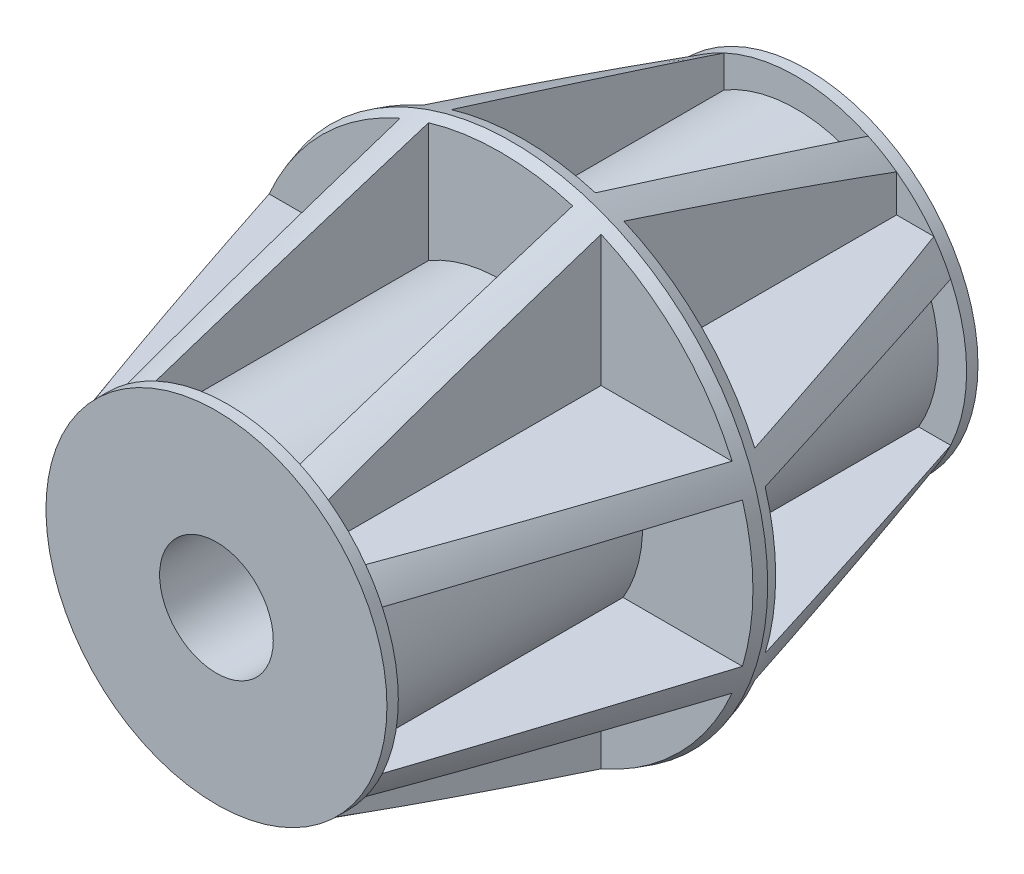
SolidWorks part; units mm, degrees
note: The reader was unsure of these and kept them because the rebuilt part matched: shared geometry of "Cross Cut Sketch<2>".
ref_plane "Front Plane" through (0, 0, 0) normal (0, 0, 1) x (1, 0, 0)
ref_plane "Top Plane" through (0, 0, 0) normal (0, 1, 0) x (1, 0, 0)
ref_plane "Right Plane" through (0, 0, 0) normal (1, 0, 0) x (0, 0, -1)
sketch "Front Connector Sketch" plane through (0, 0, 0) normal (0, 0, 1) x (1, 0, 0)
  circle A0 centre (0, 0) radius 30
  dimension "D1" = 60
extrude "Front Connector Extrude" add sketch "Front Connector Sketch" against normal blind 2
ref_plane "Back Plane" through (0, 0, 100) normal (0, 0, 1) x (1, 0, 0)
sketch "Back Connector Sketch" plane through (0, 0, 100) normal (0, 0, 1) x (1, 0, 0)
  circle A0 centre (0, 0) radius 30
  circle A1 centre (0, 0) radius 30 construction
extrude "Back Connector Extrude" add sketch "Back Connector Sketch" along normal blind 2 separate body
ref_plane "Mid Plane" through (0, 0, 50) normal (0, 0, 1) x (1, 0, 0)
sketch "Mid Ring Sketch" plane through (0, 0, 50) normal (0, 0, 1) x (1, 0, 0)
  circle A0 centre (0, 0) radius 45
  dimension "D1" = 90
loft "Front Loft" add profiles "Mid Ring Sketch" section face at (30, 0, 0) section "Mid Ring Sketch" connector at (0.9235, -29.9858, 0) connector at (0.2748, -44.9992, 50)
loft "Back Loft" add section edge at (45, 0, 50) section face at (30, 0, 100) connector at (44.9951, 0.6652, 50) connector at (29.9954, 0.5232, 100)
sketch "Cross Cut Sketch" plane through (0, 0, 50) normal (0, 0, 1) x (1, 0, 0)
  line L0 (-12.6777, 43.1773) -> (-12.6777, 21.5471)
  line L1 (-12.6777, 21.5471) -> (-12.6777, 17.6777) construction
  line L2 (-12.6777, -21.5471) -> (-12.6777, -43.1773)
  line L3 (12.6777, 43.1773) -> (12.6777, 21.5471)
  line L4 (12.6777, 21.5471) -> (12.6777, 17.6777) construction
  line L5 (12.6777, -21.5471) -> (12.6777, -43.1773)
  line L6 (17.6777, 41.3824) -> (17.6777, 17.6777)
  line L7 (17.6777, 12.6777) -> (17.6777, -12.6777) construction
  line L8 (17.6777, -17.6777) -> (17.6777, -41.3824)
  line L9 (-17.6777, 41.3824) -> (-17.6777, 17.6777)
  line L10 (-17.6777, 12.6777) -> (-17.6777, -12.6777) construction
  line L11 (-17.6777, -17.6777) -> (-17.6777, -41.3824)
  line L16 (-41.3824, 17.6777) -> (-17.6777, 17.6777)
  line L17 (-12.6777, 17.6777) -> (12.6777, 17.6777) construction
  line L18 (17.6777, 17.6777) -> (41.3824, 17.6777)
  line L20 (43.1773, 12.6777) -> (21.5471, 12.6777)
  line L21 (21.5471, 12.6777) -> (17.6777, 12.6777) construction
  line L22 (-21.5471, 12.6777) -> (-43.1773, 12.6777)
  line L24 (-43.1773, -12.6777) -> (-21.5471, -12.6777)
  line L25 (-21.5471, -12.6777) -> (-17.6777, -12.6777) construction
  line L26 (21.5471, -12.6777) -> (43.1773, -12.6777)
  line L28 (41.3824, -17.6777) -> (17.6777, -17.6777)
  line L29 (12.6777, -17.6777) -> (-12.6777, -17.6777) construction
  line L30 (-17.6777, -17.6777) -> (-41.3824, -17.6777)
  line L32 (-17.6777, 12.6777) -> (-21.5471, 12.6777) construction
  line L33 (-12.6777, -12.6777) -> (12.6777, -12.6777) construction
  line L34 (-12.6777, -17.6777) -> (-12.6777, -21.5471) construction
  line L35 (12.6777, -17.6777) -> (12.6777, -21.5471) construction
  line L36 (17.6777, -12.6777) -> (21.5471, -12.6777) construction
  line L37 (12.6777, 12.6777) -> (-12.6777, 12.6777) construction
  line L38 (12.6777, 12.6777) -> (12.6777, -12.6777) construction
  line L39 (-12.6777, 12.6777) -> (-12.6777, -12.6777) construction
  arc A0 (-17.6777, 41.3824) -> (-41.3824, 17.6777) centre (0, 0) ccw
  circle A1 centre (0, 0) radius 45 construction
  arc A2 (-21.5471, 12.6777) -> (-21.5471, -12.6777) centre (0, 0) ccw
  arc A4 (-12.6777, -43.1773) -> (12.6777, -43.1773) centre (0, 0) ccw
  arc A5 (-12.6777, -21.5471) -> (12.6777, -21.5471) centre (0, 0) ccw
  arc A6 (-43.1773, 12.6777) -> (-43.1773, -12.6777) centre (0, 0) ccw
  arc A7 (-41.3824, -17.6777) -> (-17.6777, -41.3824) centre (0, 0) ccw
  arc A8 (21.5471, -12.6777) -> (21.5471, 12.6777) centre (0, 0) ccw
  arc A9 (43.1773, -12.6777) -> (43.1773, 12.6777) centre (0, 0) ccw
  arc A10 (12.6777, 43.1773) -> (-12.6777, 43.1773) centre (0, 0) ccw
  arc A11 (17.6777, -41.3824) -> (41.3824, -17.6777) centre (0, 0) ccw
  arc A12 (12.6777, 21.5471) -> (-12.6777, 21.5471) centre (0, 0) ccw
  arc A13 (41.3824, 17.6777) -> (17.6777, 41.3824) centre (0, 0) ccw
  circle A14 centre (0, 0) radius 30 construction
  point P19 (12.6777, 0)
  point P47 (-17.6777, 17.6777)
  point P72 (0, 12.6777)
  dimension "D1" = 5
  dimension "D3" = 5
  dimension "D2" = 5
extrude "Back Cross Cut" cut sketch "Cross Cut Sketch" along normal up to surface (48 mm away) from offset 2
extrude "Front Cross Cut" cut sketch "Cross Cut Sketch<2>" against normal up to surface (48 mm away) from offset 2
sketch "Cross Cut Sketch<2>" plane through (0, 0, 50) normal (0, 0, 1) x (1, 0, 0) same geometry as "Cross Cut Sketch"
sketch "Pin Hole Sketch" plane through (0, 0, 100) normal (0, 0, 1) x (1, 0, 0)
  circle A0 centre (0, 0) radius 10
  dimension "D1" = 20
extrude "Pin Hole Cut" cut sketch "Pin Hole Sketch" against normal blind 40 and the other way up to surface (2 mm away) other way up to face at (30, 0, 102)
